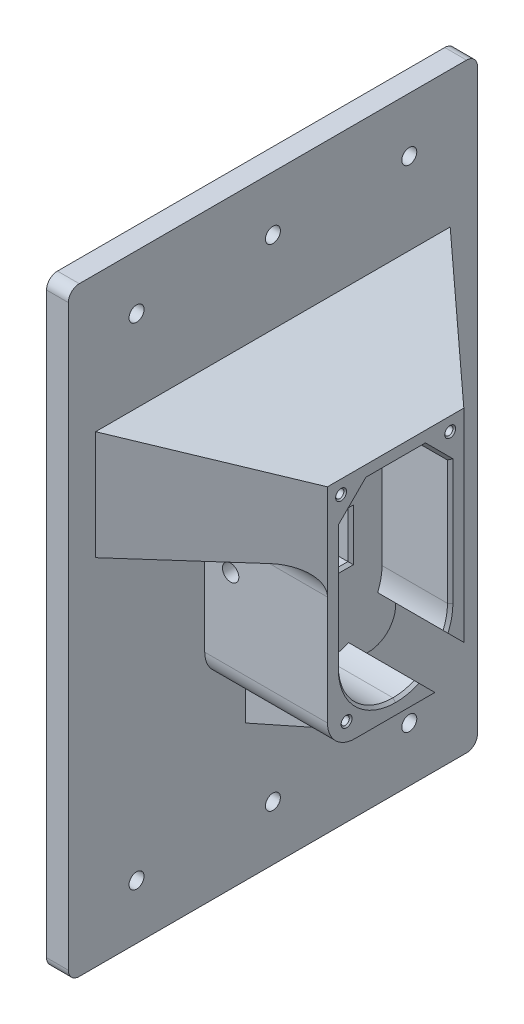
SolidWorks part; units mm, degrees
ref_plane "前视基准面" through (0, 0, 0) normal (0, 0, 1) x (1, 0, 0)
ref_plane "上视基准面" through (0, 0, 0) normal (0, 1, 0) x (1, 0, 0)
ref_plane "右视基准面" through (0, 0, 0) normal (1, 0, 0) x (0, 0, -1)
other "Configuration Table"
sketch "草图1" plane through (0, 0, 0) normal (1, 0, 0) x (0, 0, -1)
  line L1 (-65, 60) -> (65, 60)
  line L2 (-65, 60) -> (-65, -60)
  line L3 (-65, -60) -> (65, -60)
  line L4 (65, 60) -> (65, -60)
  dimension "D1" = 130
  dimension "D2" = 120
  dimension "D3" = 65
  dimension "D4" = 60
extrude "凸台-拉伸1" add sketch "草图1" along normal blind 8
sketch "草图3" plane through (8, 0, 0) normal (1, 0, 0) x (0, 0, -1)
  line L1 (-25, 45) -> (25, 45)
  line L2 (-25, 45) -> (-25, -40)
  line L3 (-25, -40) -> (25, -40)
  line L4 (25, 45) -> (25, -40)
  dimension "D1" = 85
  dimension "D2" = 50
  dimension "D3" = 25
  dimension "D4" = 40
extrude "凸台-拉伸2" add sketch "草图3" along normal blind 20
sketch "草图4" plane through (28, 0, 0) normal (1, 0, 0) x (0, 0, -1)
  line L1 (-8.5, 8.5) -> (8.5, 8.5)
  line L2 (-8.5, 8.5) -> (-8.5, -8.5)
  line L3 (-8.5, -8.5) -> (8.5, -8.5)
  line L4 (8.5, 8.5) -> (8.5, -8.5)
  dimension "D1" = 17
  dimension "D2" = 8.5
  dimension "D3" = 8.5
extrude "切除-拉伸1" cut sketch "草图4" against normal blind 19
sketch "草图5" plane through (0, 0, -25) normal (0, 0, -1) x (-1, 0, 0)
  line L0 (-8, -60) -> (-8, 60) construction
  circle A0 centre (-17.5, 0) radius 3
  dimension "D1" = 6
  dimension "D2" = 9.5
extrude "切除-拉伸2" cut sketch "草图5" against normal through all
sketch "草图6" plane through (28, 0, 0) normal (1, 0, 0) x (0, 0, -1)
  line L0 (-20, 40) -> (-20, -35)
  line L1 (-20, -35) -> (20, -35)
  line L2 (20, -35) -> (20, 40)
  line L3 (20, 40) -> (-20, 40)
  line L4 (-25, 45) -> (-25, -40)
  line L5 (-25, -40) -> (25, -40)
  line L6 (25, -40) -> (25, 45)
  line L7 (25, 45) -> (-25, 45)
  line L8 (-25, 45) -> (-25, -40)
  line L9 (-25, -40) -> (25, -40)
  line L10 (25, -40) -> (25, 45)
  line L11 (25, 45) -> (-25, 45)
  dimension "D1" = 0
  dimension "D2" = 5
extrude "凸台-拉伸3" add sketch "草图6" along normal blind 25
chamfer "倒角1" distance 9.5 angle 45 2 edges at (40.5, 40, 20) (40.5, 40, -20)
fillet "圆角1" radius 20 2 edges at (40.5, -35, 20) (40.5, -35, -20)
sketch "草图7" plane through (53, 0, 0) normal (1, 0, 0) x (0, 0, -1)
  line L0 (0, -15) -> (30.2286, -45.2286) construction
  line L1 (0, -15) -> (50000, -15) construction
  line L2 (0, -15) -> (0, 49985) construction
  line L3 (6.0104, -31.617) -> (16.617, -21.0104)
  line L4 (16.617, -21.0104) -> (32.1734, -36.5668)
  line L5 (32.1734, -36.5668) -> (21.5668, -47.1734)
  line L6 (6.0104, -31.617) -> (21.5668, -47.1734)
  point P12 (11.3137, -26.3137)
  point P13 (26.8701, -41.8701)
  dimension "D1" = 45
  dimension "D2" = 22
  dimension "D3" = 16
  dimension "D4" = 7.5
extrude "切除-拉伸3" cut sketch "草图7" against normal up to surface (25 mm away) and the other way through all up to face at (28, 9.6737, 0)
chamfer "倒角2" distance 1 angle 45 4 edges at (28, 0, 8.5) (28, 8.5, 0) (28, 0, -8.5) (28, -8.5, 0)
chamfer "倒角3" distance 1 angle 45 8 edges at (53, -34.5993, -3.9832) (53, -29.1421, 14.1421) (53, -18.9832, -19.5993) (53, 7.75, 20) (53, 35.25, 15.25) (53, 40, 0) (53, 35.25, -15.25) (53, 7.75, -20)
sketch "草图8" plane through (0, 45, 0) normal (0, 1, 0) x (1, 0, 0)
  line L0 (53, -25) -> (8, -65)
  line L1 (8, -65) -> (8, -25)
  line L2 (8, -25) -> (53, -25)
  line L3 (0, 0) -> (50000, 0) construction
  line L4 (8, 25) -> (53, 25)
  line L5 (8, 65) -> (8, 25)
  line L6 (53, 25) -> (8, 65)
extrude "凸台-拉伸4" add sketch "草图8" against normal blind 25
sketch "草图9" plane through (0, 0, 0) normal (0, 0, 1) x (1, 0, 0)
  line L0 (53, 45) -> (8, 60)
  line L1 (8, 60) -> (8, 45)
  line L2 (8, 45) -> (53, 45)
extrude "凸台-拉伸5" add sketch "草图9" along normal up to surface and the other way up to surface up to face at (30.5, 32.5, 45) other way up to face at (30.5, 32.5, -45)
sketch "草图10" plane through (0, 0, 0) normal (0, 0, 1) x (1, 0, 0)
  line L0 (8, -60) -> (53, -40)
  line L1 (53, -40) -> (8, -40)
  line L2 (8, -40) -> (8, -60)
extrude "凸台-拉伸6" add sketch "草图10" along normal blind 10 and the other way blind 10
fillet "圆角2" radius 10 2 edges at (18, -40, -25) (30.5, -40, 25)
sketch "草图11" plane through (53, 0, 0) normal (1, 0, 0) x (0, 0, -1)
  line L0 (25, 45) -> (-25, 45) construction
  line L1 (-25, 45) -> (-25, 20) construction
  line L2 (25, 20) -> (25, 45) construction
  line L3 (-15, -40) -> (-10, -40) construction
  line L4 (-25, 20) -> (-25, -30) construction
  circle A0 centre (20, 40) radius 1.5
  circle A1 centre (-18, -33) radius 1.5
  circle A2 centre (-20, 40) radius 1.5
  dimension "D1" = 3
  dimension "D2" = 5
  dimension "D3" = 5
  dimension "D4" = 5
  dimension "D5" = 5
  dimension "D6" = 7
  dimension "D7" = 7
extrude "切除-拉伸4" cut sketch "草图11" against normal blind 20 and the other way through all
chamfer "倒角4" distance 0.5 angle 45 3 edges at (53, -33, 16.5) (53, 40, -21.5) (53, 40, 18.5)
sketch "草图13" plane through (0, 0, 0) normal (-1, 0, 0) x (0, 0, 1)
  line L4 (65, -60) -> (65, 60)
  line L5 (65, 60) -> (-65, 60)
  line L6 (-65, 60) -> (-65, -60)
  line L7 (-65, -60) -> (65, -60)
  line L8 (65, -60) -> (65, 60)
  line L9 (65, 60) -> (-65, 60)
  line L10 (-65, 60) -> (-65, -60)
  line L11 (-65, -60) -> (65, -60)
  line L13 (-75, 110) -> (75, 110)
  line L14 (-75, 110) -> (-75, -110)
  line L15 (-75, -110) -> (75, -110)
  line L16 (75, 110) -> (75, -110)
  dimension "D2" = 10
  dimension "D3" = 10
  dimension "D4" = 50
  dimension "D5" = 50
  dimension "D1" = 0
extrude "凸台-拉伸7" add sketch "草图13" against normal blind 8
fillet "圆角4" radius 10 2 edges at (30.5, 20, 25) (30.5, 20, -25)
sketch "草图15" plane through (8, 0, 0) normal (1, 0, 0) x (0, 0, -1)
  line L0 (0, 0) -> (50000, 0) construction
  circle A0 centre (0, 90) radius 2.75
  circle A1 centre (50, 90) radius 2.75
  circle A2 centre (-50, 90) radius 2.75
  circle A3 centre (-50, -90) radius 2.75
  circle A4 centre (50, -90) radius 2.75
  circle A5 centre (0, -90) radius 2.75
  dimension "D1" = 5.5
  dimension "D2" = 50
  dimension "D3" = 50
  dimension "D4" = 90
extrude "切除-拉伸6" cut sketch "草图15" against normal through all
fillet "圆角5" radius 4 4 edges at (4, 110, 75) (4, 110, -75) (4, -110, 75) (4, -110, -75)
